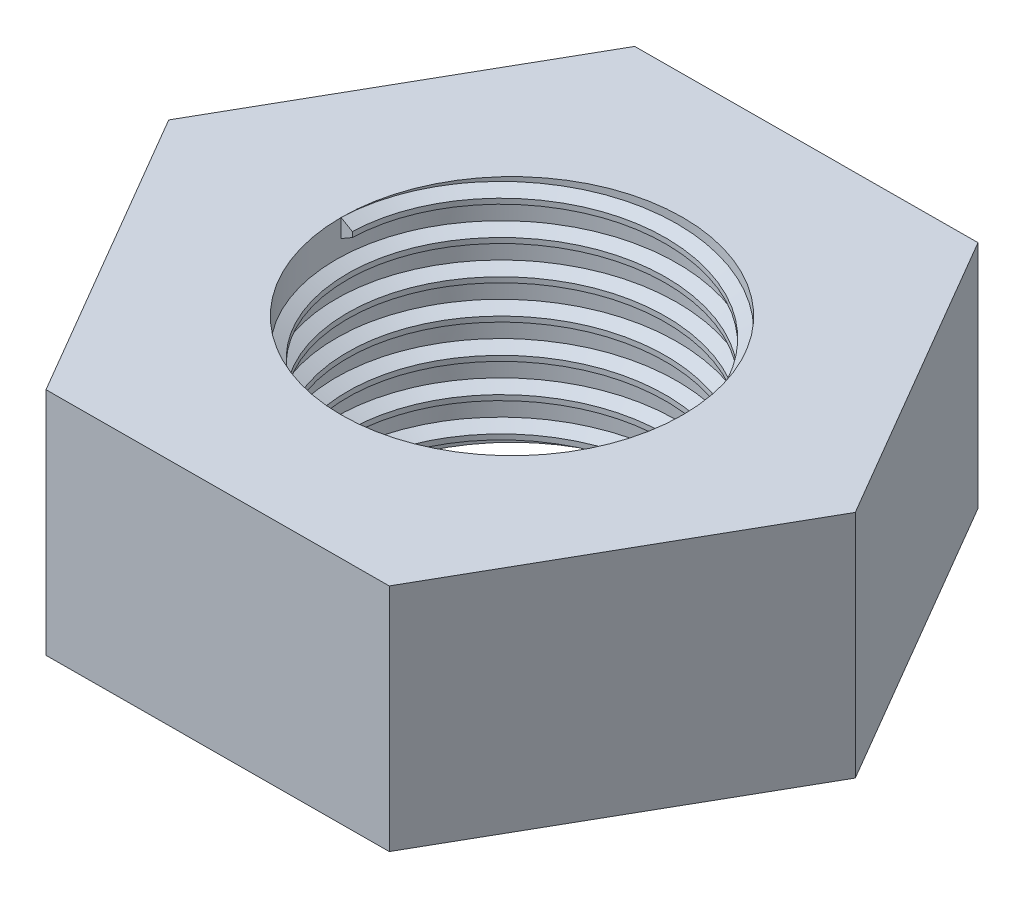
SolidWorks part; units mm, degrees
material "Plain Carbon Steel"
ref_plane "Front Plane" through (0, 0, 0) normal (0, 0, 1) x (1, 0, 0)
ref_plane "Top Plane" through (0, 0, 0) normal (0, 1, 0) x (1, 0, 0)
ref_plane "Right Plane" through (0, 0, 0) normal (1, 0, 0) x (0, 0, -1)
sketch "Sketch1" plane through (0, 0, 0) normal (0, 1, 0) x (1, 0, 0)
  line L1 (2.5758, 4.5128) -> (-2.6203, 4.4871)
  line L2 (-2.6203, 4.4871) -> (-5.1961, -0.0257)
  line L3 (-5.1961, -0.0257) -> (-2.5758, -4.5128)
  line L4 (-2.5758, -4.5128) -> (2.6203, -4.4871)
  line L5 (2.6203, -4.4871) -> (5.1961, 0.0257)
  line L6 (5.1961, 0.0257) -> (2.5758, 4.5128)
  circle A0 centre (0, 0) radius 4.5 construction
  dimension "D1" = 9
extrude "Boss-Extrude1" add sketch "Sketch1" along normal blind 3.5
sketch "Sketch2" plane through (0, 3.5, 0) normal (0, 1, 0) x (1, 0, 0)
  circle A0 centre (0, 0) radius 2.6
  dimension "D1" = 5.2
extrude "Cut-Extrude1" cut sketch "Sketch2" against normal up to next
thread "Thread1" pitch 0.3175 method extrude profile "Thread Profile1" start angle 0, offset 0, length 0, pitch 0.5175, diameter 5.2
ref_plane "Plane1" through (-2.6, 3.5, 0) normal (0, 0, 1) x (-1, 0, 0)
sketch "Thread Profile1" plane through (-2.6, 3.5, 0) normal (0, 0, 1) x (-1, 0, 0)
  line L0 (0, 0) -> (0, 0.3175) construction
  line L11 (0, 0) -> (0, 0.2778)
  line L12 (0, 0.2778) -> (-0.1719, 0.1786)
  line L13 (-0.1719, 0.1786) -> (-0.1719, 0.0992)
  line L15 (-0.1719, 0.0992) -> (0, 0)
  line L17 (-0.1719, 0.1389) -> (0, 0.1389) construction
  point P2 (0, 0)
  dimension "Pitch" = 0.3175
  dimension "Profile_Angle" = 60
  dimension "Profile_Land" = 0.0794
  dimension "Profile_Height" = 0.1719
